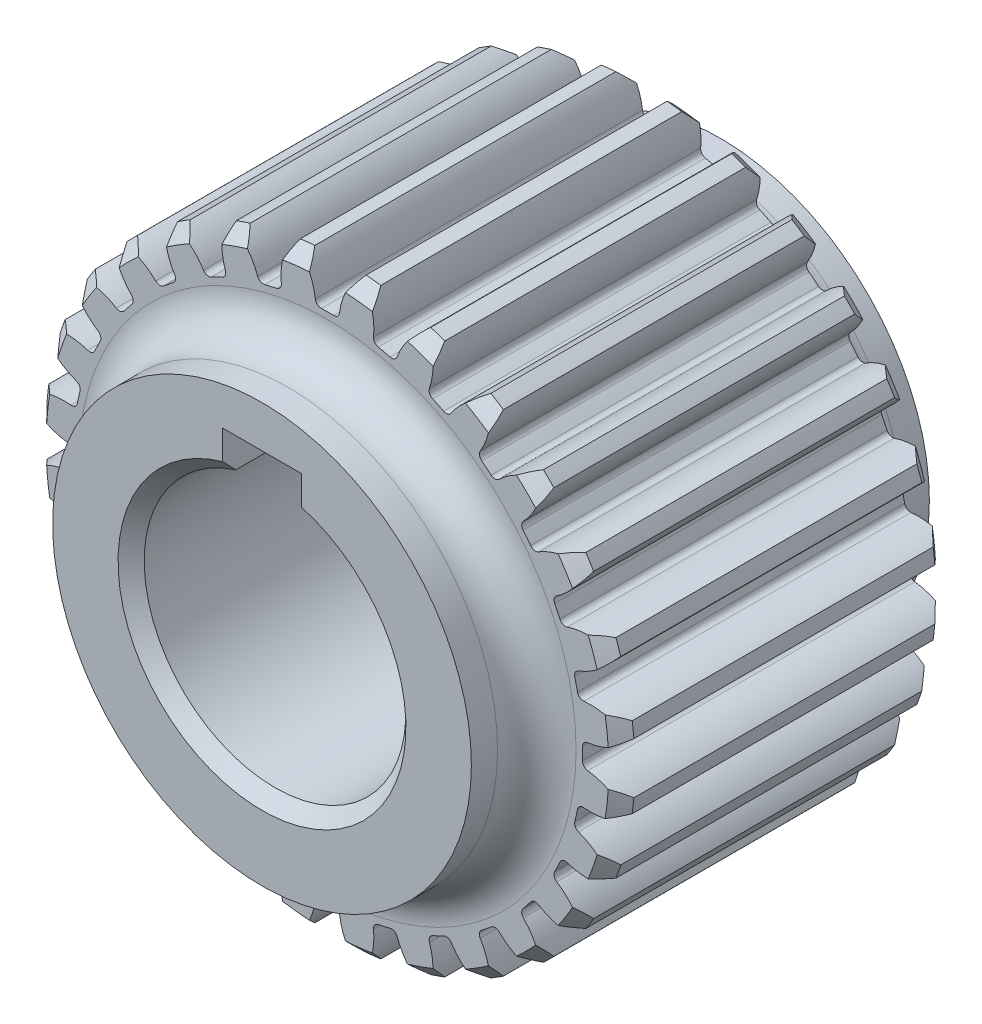
SolidWorks part; units mm, degrees
ref_plane "Front Plane" through (0, 0, 0) normal (0, 0, 1) x (1, 0, 0)
ref_plane "Top Plane" through (0, 0, 0) normal (0, 1, 0) x (1, 0, 0)
ref_plane "Right Plane" through (0, 0, 0) normal (1, 0, 0) x (0, 0, -1)
sketch "Sketch1" plane through (0, 0, 0) normal (0, 0, 1) x (1, 0, 0)
  circle A0 centre (0, 0) radius 16
  circle A1 centre (0, 0) radius 22.5
  dimension "D1" = 32
  dimension "D2" = 45
extrude "Boss-Extrude1" add sketch "Sketch1" along normal mid plane 35 contours A0
extrude "Boss-Extrude2" add sketch "Sketch1<3>" along normal mid plane 25 contours A1 A0 region at (-21.8636, 0, 0)
sketch "Sketch1<3>" plane through (0, 0, 0) normal (0, 0, 1) x (1, 0, 0) same geometry as "Sketch1"
chamfer "Chamfer1" distance 1 angle 45 2 edges at (22.5, 0, -12.5) (22.5, 0, 12.5)
fillet "Fillet1" radius 3 2 edges at (16, 0, -12.5) (16, 0, 12.5)
sketch "Sketch3" plane through (0, 0, 12.5) normal (0, 0, 1) x (1, 0, 0)
  line L0 (0, 0) -> (0, 22.5) construction
  line L1 (0, 0) -> (5.0078, 21.9356) construction
  line L2 (0, 0) -> (2.5198, 22.3585) construction
  line L3 (-0.89, 19.4797) -> (0, 0) construction
  line L4 (-1.1777, 20.9669) -> (1.1777, 20.9669) construction
  line L5 (1.1777, 20.9669) -> (3.5184, 20.7032) construction
  line L6 (-2.4735, 24.5282) -> (0, 17.7323) construction
  circle A0 centre (0, 0) radius 21 construction
  arc A2 (1.9583, 22.4146) -> (-1.9583, 22.4146) centre (0, 0) ccw
  arc A3 (0.89, 19.4797) -> (-0.89, 19.4797) centre (0, 0) ccw
  arc A4 (1.9583, 22.4146) -> (0.89, 19.4797) centre (6.1115, 19.2411) ccw
  arc A5 (-1.9583, 22.4146) -> (-0.89, 19.4797) centre (-6.1115, 19.2411) cw
  point P14 (-1.1998, 21.0288)
  dimension "D2" = 42
  dimension "D3" = 45
  dimension "D1" = 19.5
  dimension "D4" = 12.86
  dimension "D5" = 20
extrude "Cut-Extrude1" cut sketch "Sketch3" against normal through all both and the other way through all
fillet "Fillet2" radius 0.45 2 edges at (0.89, 19.4797, 0) (-0.89, 19.4797, 0)
pattern_circular "CirPattern3" count 28 over 360 about axis through (0, 0, 12.5) along (0, 0, -1) of "Fillet2", "Cut-Extrude1" reverse direction yes
sketch "Sketch4" plane through (0, 0, 17.5) normal (0, 0, 1) x (1, 0, 0)
  line L0 (0, 19) -> (0, -19) construction
  line L1 (0, -10) -> (0, -16) construction
  line L2 (3, 12.8) -> (-3, 12.8)
  line L3 (-3, 12.8) -> (-3, 9.5394)
  line L4 (3, 12.8) -> (3, 9.5394)
  arc A0 (-3, 9.5394) -> (3, 9.5394) centre (0, 0) ccw
  circle A1 centre (0, 0) radius 19 construction
  circle A2 centre (0, 0) radius 16 construction
  point P15 (0, 12.8)
  dimension "D1" = 20
  dimension "D2" = 6
  dimension "D3" = 22.8
extrude "Cut-Extrude2" cut sketch "Sketch4" against normal through all both
chamfer "Chamfer2" distance 1 angle 45 2 edges at (0, -10, 17.5) (0, -10, -17.5)
equation "\"M\"= 1.5"
equation "\"Z\"= 28"
equation "\"Angle\"= 20"
equation "\"D\"= 42"
equation "\"Da\"= ( \"Z\" + 2 ) * \"M\""
equation "\"Df\"= ( \"Z\" - 2 ) * \"M\""
equation "\"D2@Sketch3\"= \"D\""
equation "\"D3@Sketch3\"= \"Da\""
equation "\"D5@Sketch3\"=\"Angle\""
